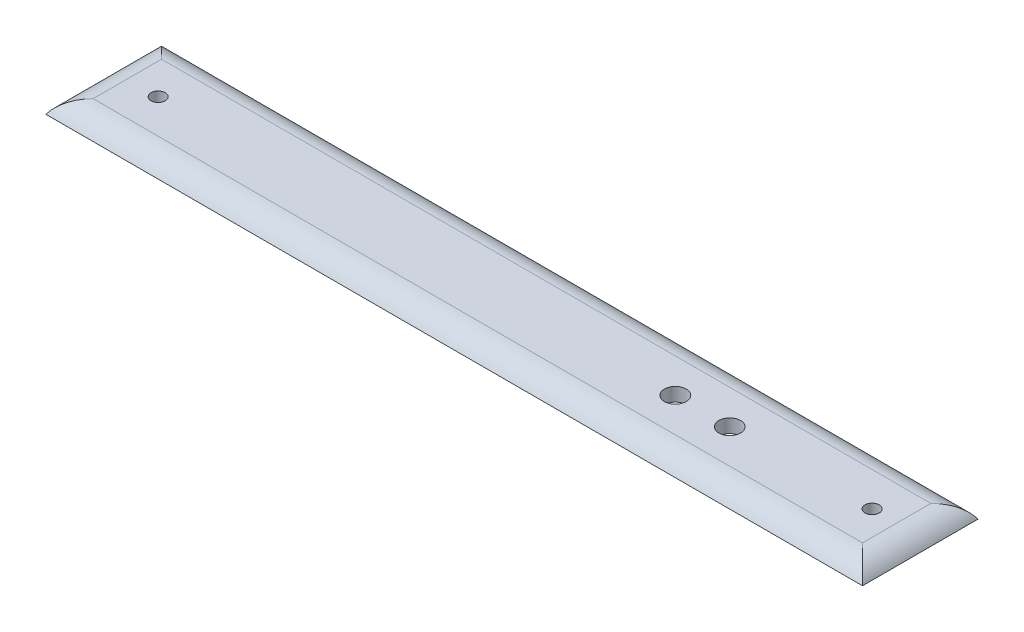
SolidWorks part; units mm, degrees
ref_plane "前视基准面" through (0, 0, 0) normal (0, 0, 1) x (1, 0, 0)
ref_plane "上视基准面" through (0, 0, 0) normal (0, 1, 0) x (1, 0, 0)
ref_plane "右视基准面" through (0, 0, 0) normal (1, 0, 0) x (0, 0, -1)
other "Configuration Table"
sketch "草图1" plane through (0, 0, 0) normal (0, 1, 0) x (1, 0, 0)
  line L1 (-129, 21.215) -> (129, 21.215)
  line L2 (-129, 21.215) -> (-129, -21.215)
  line L3 (-129, -21.215) -> (129, -21.215)
  line L4 (129, 21.215) -> (129, -21.215)
  line L5 (0, -21.215) -> (0, 21.215) construction
  line L6 (-129, 0) -> (129, 0) construction
  line L7 (-150, 21.215) -> (150, 21.215)
  line L8 (-150, 21.215) -> (-150, -21.215)
  line L9 (-150, -21.215) -> (150, -21.215)
  line L10 (150, 21.215) -> (150, -21.215)
  line L11 (0, -21.215) -> (0, 21.215) construction
  line L12 (-150, 0) -> (150, 0) construction
  circle A2 centre (-130, 0) radius 2.6
  circle A3 centre (132.3, 0) radius 2.6
  point P0 (0, 0)
  point P4 (0, 0)
  dimension "D4" = 5.2
  dimension "D5" = 5.2
  dimension "D6" = 20
  dimension "D7" = 17.7
  dimension "D1" = 258
  dimension "D2" = 42.43
  dimension "D3" = 300
extrude "凸台-拉伸1" add sketch "草图1" along normal blind 5 contours L2 L7 L8 L9 | L2 L3 L4 L1 | L4 L9 L10 L7 region at (0.0651, 0, 0) region at (-139.6597, 0, 0) region at (139.6758, 0, 0)
fillet "圆角1" radius 10 4 edges at (150, 5, 0) (0, 5, 21.215) (-150, 5, 0) (0, 5, -21.215)
sketch "草图2" plane through (0, 5, 0) normal (0, 1, 0) x (1, 0, 0)
  line L0 (-130, 0) -> (132.3, 0)
  line L2 (150, 21.215) -> (150, -21.215) construction
  circle A0 centre (60, 0) radius 4
  circle A1 centre (80, 0) radius 4
  dimension "D1" = 8
  dimension "D2" = 8
  dimension "D3" = 20
  dimension "D4" = 70
extrude "切除-拉伸1" cut sketch "草图2" against normal blind 10 contours L0 A0 | L0 A0 | L0 A1 | L0 A1 region at (60, 5, -1.6977) region at (80, 5, -1.6977) region at (80, 5, 1.6977) region at (60, 5, 1.6977)
